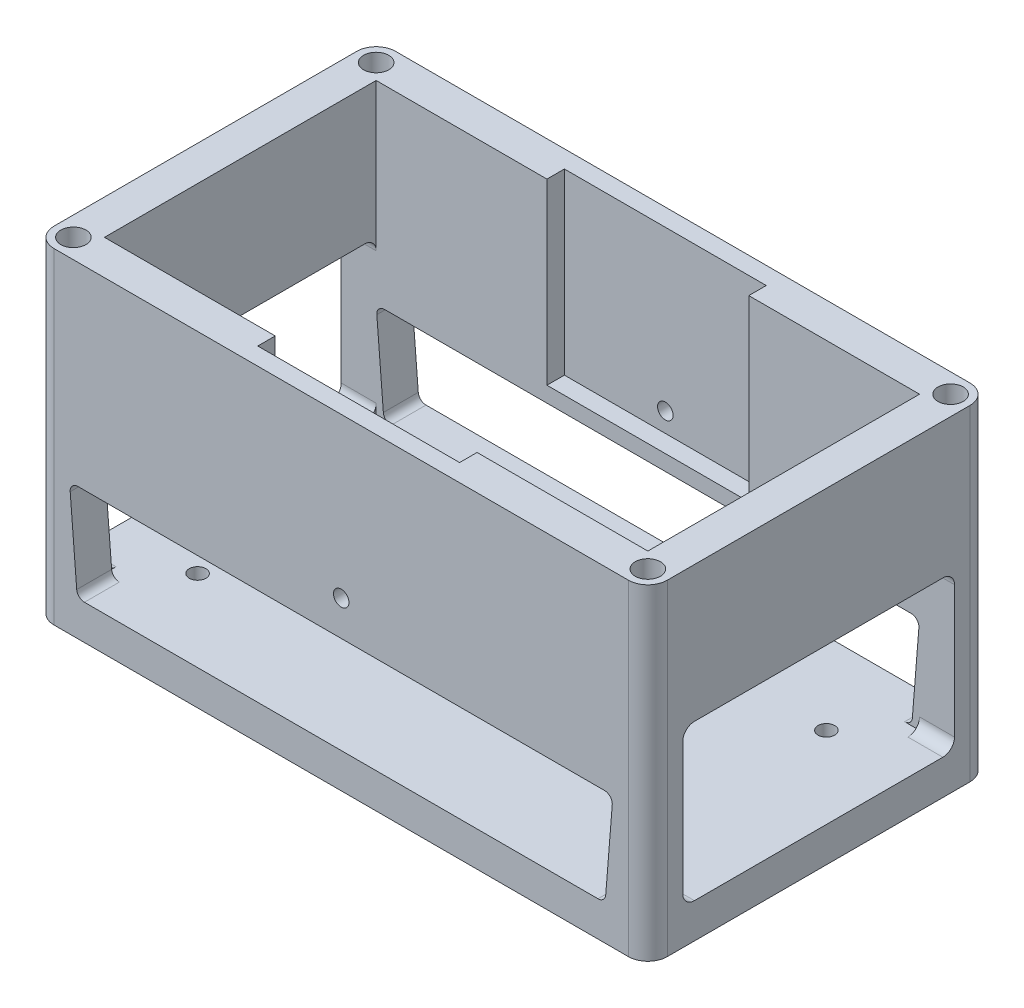
SolidWorks part; units mm, degrees
ref_plane "Front Plane" through (0, 0, 0) normal (0, 0, 1) x (1, 0, 0)
ref_plane "Top Plane" through (0, 0, 0) normal (0, 1, 0) x (1, 0, 0)
ref_plane "Right Plane" through (0, 0, 0) normal (1, 0, 0) x (0, 0, -1)
sketch "Base" plane through (0, 0, 0) normal (0, 1, 0) x (1, 0, 0)
  line L0 (0, 0) -> (0, 0.2831) construction
  line L1 (-4.145, 0) -> (-1.9108, 0) construction
  line L3 (-39.5, 22) -> (39.5, 22)
  line L4 (-39.5, 22) -> (-39.5, -22)
  line L5 (-39.5, -22) -> (39.5, -22)
  line L6 (39.5, 22) -> (39.5, -22)
  line L7 (-39.5, 22) -> (39.5, -22) construction
  line L8 (-39.5, -22) -> (39.5, 22) construction
  line L9 (-29, 11.5) -> (29, 11.5) construction
  line L10 (-29, 11.5) -> (-29, -11.5) construction
  line L11 (-29, -11.5) -> (29, -11.5) construction
  line L12 (29, 11.5) -> (29, -11.5) construction
  line L13 (-29, 11.5) -> (29, -11.5) construction
  line L14 (-29, -11.5) -> (29, 11.5) construction
  line L15 (27, 10.3453) -> (29, 9.1906)
  line L16 (29, 9.1906) -> (31, 10.3453)
  line L17 (31, 10.3453) -> (31, 12.6547)
  line L18 (31, 12.6547) -> (29, 13.8094)
  line L19 (29, 13.8094) -> (27, 12.6547)
  line L20 (27, 12.6547) -> (27, 10.3453)
  line L21 (-31, 10.3453) -> (-29, 9.1906)
  line L22 (-29, 9.1906) -> (-27, 10.3453)
  line L23 (-27, 10.3453) -> (-27, 12.6547)
  line L24 (-27, 12.6547) -> (-29, 13.8094)
  line L25 (-29, 13.8094) -> (-31, 12.6547)
  line L26 (-31, 12.6547) -> (-31, 10.3453)
  line L27 (-31, -12.6547) -> (-29, -13.8094)
  line L28 (-29, -13.8094) -> (-27, -12.6547)
  line L29 (-27, -12.6547) -> (-27, -10.3453)
  line L30 (-27, -10.3453) -> (-29, -9.1906)
  line L31 (-29, -9.1906) -> (-31, -10.3453)
  line L32 (-31, -10.3453) -> (-31, -12.6547)
  line L33 (27, -12.6547) -> (29, -13.8094)
  line L34 (29, -13.8094) -> (31, -12.6547)
  line L35 (31, -12.6547) -> (31, -10.3453)
  line L36 (31, -10.3453) -> (29, -9.1906)
  line L37 (29, -9.1906) -> (27, -10.3453)
  line L38 (27, -10.3453) -> (27, -12.6547)
  circle A0 centre (-29, -11.5) radius 1.075
  circle A1 centre (-29, 11.5) radius 1.075
  circle A2 centre (29, 11.5) radius 1.075
  circle A3 centre (29, -11.5) radius 1.075
  circle A4 centre (29, 11.5) radius 2 construction
  circle A5 centre (-29, 11.5) radius 2 construction
  circle A6 centre (-29, -11.5) radius 2 construction
  circle A7 centre (29, -11.5) radius 2 construction
  point P5 (0, 0)
  point P12 (0, 0)
  dimension "D5" = 2.15
  dimension "D6" = 4
  dimension "D1" = 79
  dimension "D2" = 44
  dimension "D3" = 23
  dimension "D4" = 58
extrude "Boss-Extrude1" add sketch "Base" along normal blind 42 contours L31 L32 L27 L28 L29 L30 A0 | A0 | L6 L3 L4 L5 L38 L37 L36 L35 L34 L33 L32 L31 L30 L29 L28 L27 L26 L25 L24 L23 L22 L21 L20 L19 L18 L17 L16 L15 | L25 L26 L21 L22 L23 L24 A1 | A1 | A3 | L37 L38 L33 L34 L35 L36 A3 | A2 | L19 L20 L15 L16 L17 L18 A2 region at (0, 0, 0) region at (27.0611, 0, -11.5) region at (-30.9389, 0, -11.5) region at (-30.9389, 0, 11.5) region at (27.0611, 0, 11.5) region at (-29, 0, 11.5) region at (-29, 0, -11.5) region at (29, 0, -11.5) region at (29, 0, 11.5)
shell "Shell1" thickness 4.5 removed face at (0, 42, 0)
extrude "Cut-Extrude2" cut sketch "Base<7>" against normal through all from surface contours A0 | A1 | A3 | A2 region at (-29, 0, 11.5) region at (-29, 0, -11.5) region at (29, 0, -11.5) region at (29, 0, 11.5) starting at face at (0, 4.5, 0)
sketch "Base<7>" plane through (0, 0, 0) normal (0, 1, 0) x (1, 0, 0) same geometry as "Base"
extrude "Cut-Extrude3" cut sketch "Base<8>" along normal blind 2 contours L19 L20 L15 L16 L17 L18 A2 | L37 L38 L33 L34 L35 L36 A3 | L31 L32 L27 L28 L29 L30 A0 | L25 L26 L21 L22 L23 L24 A1 region at (27.0611, 0, -11.5) region at (-30.9389, 0, -11.5) region at (-30.9389, 0, 11.5) region at (27.0611, 0, 11.5)
sketch "Base<8>" plane through (0, 0, 0) normal (0, 1, 0) x (1, 0, 0) same geometry as "Base"
sketch "Sketch3" plane through (0, 42, 0) normal (0, 1, 0) x (1, 0, 0)
  line L0 (0, -22) -> (0, 22) construction
  line L1 (-39.5, 22) -> (39.5, 22) construction
  line L2 (-39.5, -22) -> (39.5, -22) construction
  line L3 (-39.5, 0) -> (39.5, 0) construction
  line L4 (39.5, 22) -> (39.5, -22) construction
  line L5 (-39.5, 22) -> (-39.5, -22) construction
  line L6 (0, 17.5) -> (0, 22) construction
  line L7 (-13, 19.75) -> (13, 19.75)
  line L8 (-13, 19.75) -> (-13, -19.75)
  line L9 (-13, -19.75) -> (13, -19.75)
  line L10 (13, 19.75) -> (13, -19.75)
  line L11 (-13, 19.75) -> (13, -19.75) construction
  line L12 (-13, -19.75) -> (13, 19.75) construction
  line L13 (-35, 17.5) -> (35, 17.5) construction
  point P2 (0, 0)
  point P22 (0, 19.75)
  dimension "D1" = 26
extrude "Cut-Extrude4" cut sketch "Sketch3" against normal blind 23
sketch "SD_CARD" plane through (-39.5, 0, 0) normal (-1, 0, 0) x (0, 0, 1)
  line L0 (-22, 4.5) -> (22, 4.5) construction
  line L1 (-22, 42) -> (-22, 0) construction
  line L2 (22, 42) -> (22, 0) construction
  line L3 (-10.425, 4.5) -> (-12.575, 4.5) construction
  line L4 (-16, 4.5) -> (16, 4.5)
  line L5 (-17.5, 6) -> (-17.5, 23)
  line L6 (17.5, 6) -> (17.5, 23)
  line L7 (-16, 24.5) -> (16, 24.5)
  line L8 (0, 0) -> (0, 42) construction
  line L9 (-22, 0) -> (22, 0) construction
  line L10 (-22, 42) -> (22, 42) construction
  arc A0 (16, 4.5) -> (17.5, 6) centre (16, 6) ccw
  arc A1 (17.5, 23) -> (16, 24.5) centre (16, 23) ccw
  arc A2 (-17.5, 6) -> (-16, 4.5) centre (-16, 6) ccw
  arc A3 (-17.5, 23) -> (-16, 24.5) centre (-16, 23) cw
  point P20 (17.5, 4.5)
  point P23 (17.5, 24.5)
  point P26 (-17.5, 4.5)
  point P29 (-17.5, 24.5)
  dimension "D3" = 1.5
  dimension "D4" = 1.5
  dimension "D5" = 1.5
  dimension "D6" = 1.5
  dimension "D1" = 35
  dimension "D2" = 20
fillet "Fillet1" radius 2.5 4 edges at (39.5, 21, 22) (-39.5, 21, 22) (-39.5, 21, -22) (39.5, 21, -22)
sketch "INPUTS" plane through (0, 0, 22) normal (0, 0, 1) x (1, 0, 0)
  line L0 (-39.5, 4.5) -> (39.5, 4.5) construction
  line L1 (39.5, 42) -> (39.5, 0) construction
  line L2 (-35, 4.5) -> (35, 4.5) construction
  line L3 (-35, 4.5) -> (-35, 17) construction
  line L4 (35, 4.5) -> (35, 17) construction
  line L5 (-35, 17) -> (35, 17) construction
  line L14 (-35, 17) -> (35, 4.5) construction
  line L15 (35, 17) -> (-35, 4.5) construction
  line L16 (0, 0) -> (0, 26.728) construction
  line L21 (-35, 17) -> (-34, 4.5)
  line L22 (-34, 4.5) -> (34, 4.5)
  line L23 (34, 4.5) -> (35, 17)
  line L24 (35, 17) -> (-35, 17)
  point P3 (0, 10.75)
  point P9 (0, 4.5)
  dimension "D1" = 70
  dimension "D8" = 1
  dimension "12.5" = 12.5
extrude "Cut-Extrude5" cut sketch "INPUTS" against normal up to surface (4.5 mm away) contours L22 L23 L24 L21 up to face at (0, 26.875, 17.5)
extrude "Cut-Extrude6" cut sketch "SD_CARD" against normal up to surface (4.5 mm away) contours L4 A0 L6 A1 L7 A3 L5 A2 up to face at (-35, 22, 3.5)
fillet "Fillet2" radius 1 4 edges at (-35, 17, 19.75) (35, 17, 19.75) (-34, 4.5, 19.75) (34, 4.5, 19.75)
ref_plane "Plane1" through (0, 0, 0) normal (-1, 0, 0) x (0, 0, 1)
mirror "Mirror1" about plane through (0, 0, 0) normal (-1, 0, 0) of "Cut-Extrude6"
sketch "Mount" plane through (0, 42, 0) normal (0, 1, 0) x (1, 0, 0)
  line L1 (-37, 19.5) -> (37, 19.5) construction
  line L2 (-37, 19.5) -> (-37, -19.5) construction
  line L3 (-37, -19.5) -> (37, -19.5) construction
  line L4 (37, 19.5) -> (37, -19.5) construction
  line L5 (-37, 19.5) -> (37, -19.5) construction
  line L6 (-37, -19.5) -> (37, 19.5) construction
  circle A0 centre (-37, 19.5) radius 1.625
  circle A1 centre (37, 19.5) radius 1.625
  circle A2 centre (37, -19.5) radius 1.625
  circle A3 centre (-37, -19.5) radius 1.625
  arc A4 (37, -22) -> (39.5, -19.5) centre (37, -19.5) ccw construction
  point P0 (0, 0)
  dimension "D1" = 3.25
  dimension "D2" = 74
  dimension "D3" = 39
extrude "Cut-Extrude7" cut sketch "Mount" against normal blind 2.4
sketch "Camera_Mount_Hole" plane through (0, 0, 22) normal (0, 0, 1) x (1, 0, 0)
  line L0 (-11.1961, 19) -> (9.0296, 19) construction
  line L1 (-13, 19) -> (13, 19) construction
  line L2 (0, 19) -> (0, 24) construction
  line L3 (0, 21.45) -> (0, -21.45) construction
  circle A1 centre (0, 21.5) radius 1
  point P10 (0, 21.5)
  dimension "D3" = 2
extrude "Cut-Extrude8" cut sketch "Camera_Mount_Hole" against normal up to surface (2.25 mm away) and the other way through all contours A1 region at (0, 21.5, 22) up to face at (0, 30.5, 19.75)
ref_plane "Plane2" through (0, 0, 0) normal (0, 0, 1) x (1, 0, 0)
mirror "Mirror2" about plane through (0, 0, 0) normal (0, 0, 1) of "Cut-Extrude8"
mirror "Mirror3" about plane through (0, 0, 0) normal (0, 0, 1) of "Fillet2", "Cut-Extrude5"
equation "\"Wall\"= 4.5mm"
equation "\"D1@Base\" = 70.00mm + \"Wall\" * 2"
equation "\"D2@Base\" = 35 + \"Wall\" * 2"
equation "\"D1@Shell1\"=\"Wall\""
equation "\"Camera_Mount_Thickness\"= 5.0"
equation "\"D1@Camera_Mount_Hole\" = \"Camera_Mount_Thickness\""
equation "\"D1@Cut-Extrude7\"=2.4"
